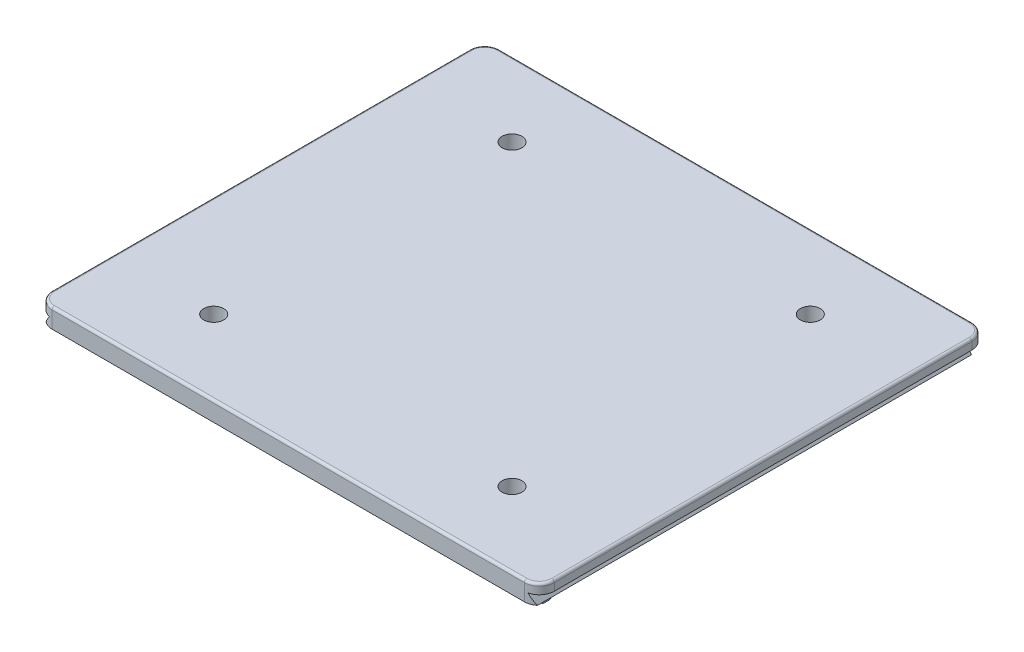
SolidWorks part; units mm, degrees
ref_plane "Front Plane" through (0, 0, 0) normal (0, 0, 1) x (1, 0, 0)
ref_plane "Top Plane" through (0, 0, 0) normal (0, 1, 0) x (1, 0, 0)
ref_plane "Right Plane" through (0, 0, 0) normal (1, 0, 0) x (0, 0, -1)
sketch "Sketch1" plane through (0, 0, 0) normal (0, 0, 1) x (1, 0, 0)
  line L0 (18.5, 26) -> (19.6553, 24.35) construction
  line L5 (19.6553, 24.35) -> (19.9004, 24) construction
  line L6 (19.9004, 24) -> (-79.9004, 24) construction
  line L9 (18.5, 26) -> (19.6553, 24.35) construction
  line L10 (19.6553, 24.35) -> (19.9004, 24) construction
  line L11 (19.9004, 24) -> (-79.9004, 24) construction
  line L13 (-79.9004, 24) -> (-79.6553, 24.35) construction
  line L14 (18.1948, 26) -> (19.4202, 24.25)
  line L15 (19.4202, 24.25) -> (19.4202, 24.25)
  line L16 (19.4202, 24.25) -> (-79.4202, 24.25)
  line L17 (-79.4202, 24.25) -> (-79.4202, 24.25)
  line L19 (18.2952, 25.8566) -> (19.4202, 24.25) construction
  line L20 (18.5, 26) -> (-78.5, 26) construction
  line L21 (-79.4202, 24.25) -> (-60.7104, 53.0494) construction
  line L24 (-80.5, 26.1) -> (-80.5, 28.1)
  line L28 (18.1948, 26) -> (18.1248, 26.1)
  line L31 (-79.9004, 24) -> (-79.835, 24.0704) construction
  line L36 (-79.835, 24.0704) -> (-60.92, 53.1856) construction
  line L38 (-79.6553, 24.35) -> (-78.5, 26) construction
  line L39 (-79.4202, 24.25) -> (-78.1248, 26.1)
  line L40 (-80.5, 26.1) -> (-78.1248, 26.1)
  line L41 (-80.5, 0.5) -> (-80.5, 26) construction
  line L42 (18.1248, 26.1) -> (20.5, 26.1)
  line L43 (20.5, 26.1) -> (20.5, 28.1)
  line L44 (20.5, 28.1) -> (-80.5, 28.1)
  line L45 (20.5, 26) -> (20.5, 0.5) construction
  line L47 (19.4202, 24.25) -> (-79.4202, 24.25) construction
  point P12 (17.5, 24.25)
  point P20 (-79.4202, 24.2661)
  point P25 (-79.4037, 24.25)
  point P28 (19.3811, 24.25)
  point P30 (0, 28.9309)
  point P31 (0, 0)
  dimension "D2" = 0.25
  dimension "D3" = 2
  dimension "D4" = 0.1
  dimension "D1" = 0.25
extrude "Boss-Extrude1" add sketch "Sketch1" against normal up to surface (88 mm away)
sketch "Sketch2" plane through (0, 0, -88) normal (0, 0, -1) x (-1, 0, 0)
  line L1 (80.5, 28.1) -> (-20.5, 28.1)
  line L2 (80.5, 28.1) -> (80.5, 26.1)
  line L3 (80.5, 26.1) -> (-20.5, 26.1)
  line L4 (-20.5, 28.1) -> (-20.5, 26.1)
  line L6 (80.5, 28.1) -> (-20.5, 28.1) construction
  line L7 (80.5, 28.1) -> (80.5, 26.1) construction
extrude "Boss-Extrude2" add sketch "Sketch2" along normal up to surface (2 mm away)
sketch "Sketch3" plane through (0, 24.25, 0) normal (0, -1, 0) x (1, 0, 0)
  line L0 (19.9004, -1.5) -> (-79.9004, -1.5) construction
  line L1 (19.4202, -1.5) -> (-79.4202, -1.5)
  line L2 (-79.4202, -88) -> (-79.4202, 0) construction
  line L3 (19.4202, -88) -> (19.4202, 0) construction
  line L4 (19.4202, -1.5) -> (19.4202, -3.5)
  line L5 (19.4202, -3.5) -> (-79.4202, -3.5)
  line L6 (-79.4202, -3.5) -> (-79.4202, -1.5)
  point P2 (-78.9636, -1.5)
  point P4 (-79.4202, -1.5)
  point P5 (19.4202, -1.5)
  point P9 (-77.5, -1.5)
  point P14 (19.4202, -3.5)
  dimension "D1" = 2
extrude "Boss-Extrude3" add sketch "Sketch3" along normal blind 0.25
fillet "Fillet2" radius 0.5 2 edges at (-30, 24, -3.5) (-30, 24, -1.5)
fillet "Fillet1" radius 3 4 edges at (-80.5, 27.1, -90) (20.5, 27.1, -90) (20.5, 27.1, 0) (-80.5, 27.1, 0)
sketch "Sketch4" plane through (0, 28.1, 0) normal (0, 1, 0) x (1, 0, 0)
  line L0 (0, -2.1175) -> (0, 2.1175) construction
  line L1 (17.5, 90) -> (-77.5, 90) construction
  line L2 (-80.5, 45) -> (20.5, 45) construction
  line L6 (20.5, 87) -> (20.5, 3) construction
  line L7 (-80.5, 87) -> (-80.5, 3) construction
  line L8 (-30, 90) -> (-30, 0) construction
  line L9 (-2.1175, 0) -> (2.1175, 0) construction
  circle A0 centre (0, 75) radius 2
  circle A1 centre (0, 15) radius 2
  circle A2 centre (-60, 15) radius 2
  circle A3 centre (-60, 75) radius 2
  point P11 (20.5, 45)
  dimension "D1" = 4
  dimension "D2" = 15
extrude "Cut-Extrude1" cut sketch "Sketch4" against normal up to next
fillet "Fillet3" radius 0.5 8 edges at (-30, 28.1, -90) (20.5, 28.1, -45) (19.6213, 28.1, -89.1213) (-79.6213, 28.1, -89.1213) (-80.5, 28.1, -45) (19.6213, 28.1, -0.8787) (-79.6213, 28.1, -0.8787) (-30, 28.1, 0)
